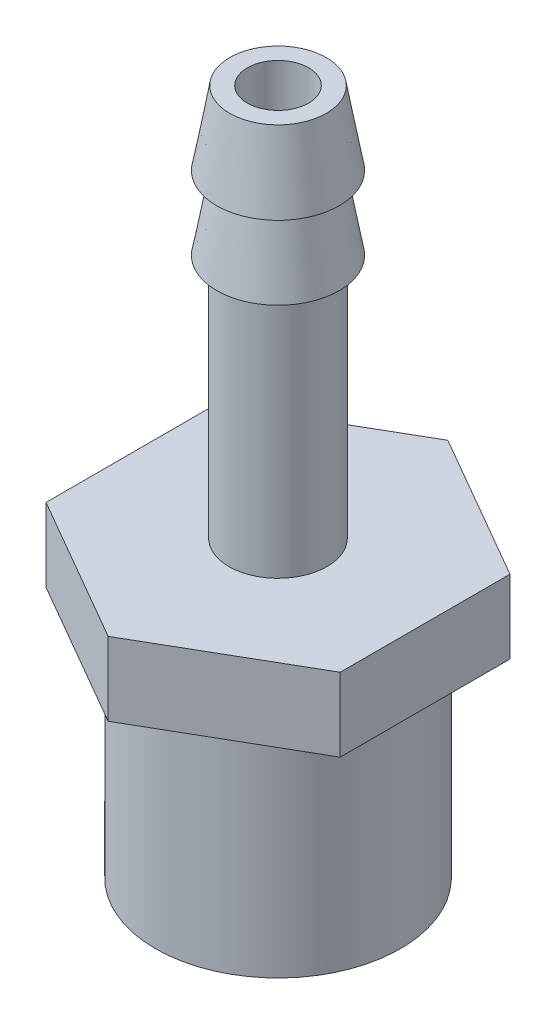
SolidWorks part; units mm, degrees
ref_plane "Plan de face" through (0, 0, 0) normal (0, 0, 1) x (1, 0, 0)
ref_plane "Plan de dessus" through (0, 0, 0) normal (0, 1, 0) x (1, 0, 0)
ref_plane "Plan de droite" through (0, 0, 0) normal (1, 0, 0) x (0, 0, -1)
sketch "Esquisse2" plane through (0, 0, 0) normal (0, 1, 0) x (1, 0, 0)
  line L0 (0, 6.9282) -> (0, 0) construction
  line L1 (0, 6.9282) -> (-6, 3.4641)
  line L2 (-6, 3.4641) -> (-6, -3.4641)
  line L3 (-6, -3.4641) -> (0, -6.9282)
  line L4 (0, -6.9282) -> (6, -3.4641)
  line L5 (6, -3.4641) -> (6, 3.4641)
  line L6 (6, 3.4641) -> (0, 6.9282)
  circle A0 centre (0, 0) radius 6 construction
  dimension "D1" = 12
extrude "Extrusion1" add sketch "Esquisse2" along normal blind 3
sketch "Esquisse3" plane through (0, 0, 0) normal (0, -1, 0) x (1, 0, 0)
  circle A0 centre (0, 0) radius 5
  circle A1 centre (0, 0) radius 3.5
  dimension "D1" = 10
  dimension "D2" = 7
extrude "Extrusion2" add sketch "Esquisse3" along normal blind 9
sketch "Esquisse4" plane through (0, 3, 0) normal (0, 1, 0) x (-1, 0, 0)
  circle A0 centre (0, 0) radius 2
  dimension "D1" = 4
extrude "Extrusion3" add sketch "Esquisse4" along normal blind 10
sketch "Esquisse5" plane through (0, 13, 0) normal (0, 1, 0) x (1, 0, 0)
  circle A0 centre (0, 0) radius 2.5
  dimension "D1" = 5
extrude "Extrusion4" add sketch "Esquisse5" along normal blind 3
chamfer "Chanfrein1" distance 3 angle 10 1 edges at (0, 16, 2.5) first distance on face at (0, 16, 2.5)
sketch "Esquisse6" plane through (0, 16, 0) normal (0, 1, 0) x (1, 0, 0)
  circle A0 centre (0, 0) radius 2.5
  dimension "D1" = 5
extrude "Extrusion5" add sketch "Esquisse6" along normal blind 3
chamfer "Chanfrein2" distance 3 angle 10 1 edges at (0, 19, 2.5) first distance on face at (0, 19, 2.5)
sketch "Esquisse7" plane through (0, 19, 0) normal (0, 1, 0) x (1, 0, 0)
  circle A0 centre (0, 0) radius 1.25
  dimension "D1" = 2.5
extrude "Extrusion6" cut sketch "Esquisse7" against normal up to next
